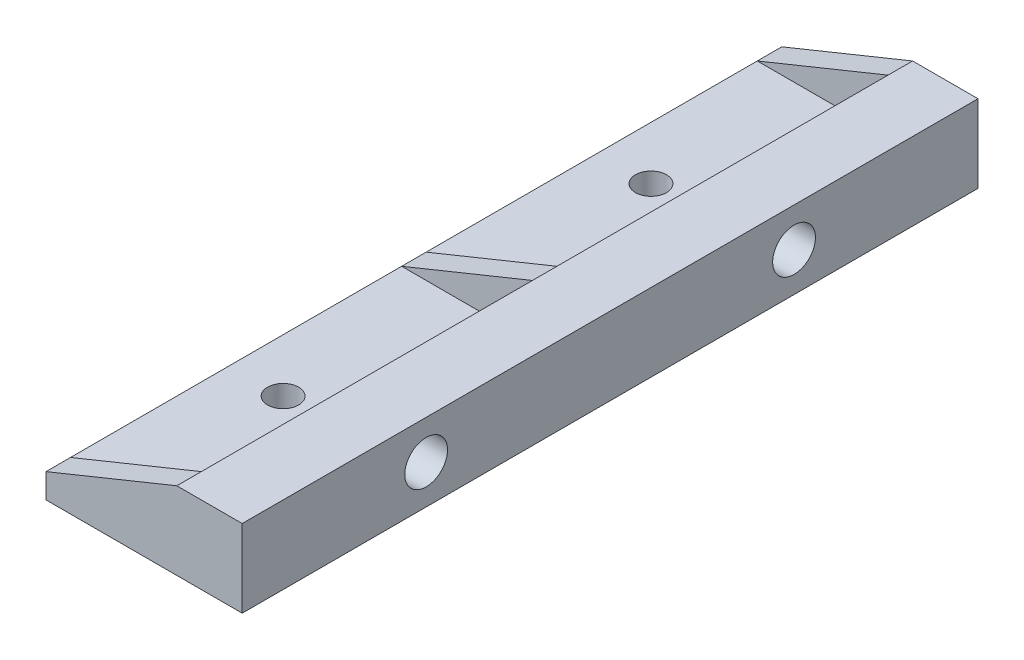
SolidWorks part; units mm, degrees
ref_plane "Front Plane" through (0, 0, 0) normal (0, 0, 1) x (1, 0, 0)
ref_plane "Top Plane" through (0, 0, 0) normal (0, 1, 0) x (1, 0, 0)
ref_plane "Right Plane" through (0, 0, 0) normal (1, 0, 0) x (0, 0, -1)
sketch "Sketch1" plane through (0, 0, 0) normal (0, 0, 1) x (1, 0, 0)
  line L0 (0, 0) -> (0, 9.5)
  line L1 (0, 9.5) -> (-8, 9.5)
  line L2 (-8, 9.5) -> (-8, 6)
  line L3 (-11, 3) -> (-24, 3)
  line L4 (-24, 3) -> (-24, 0)
  line L6 (-24, 0) -> (0, 0)
  arc A0 (-8, 6) -> (-11, 3) centre (-11, 6) cw
  dimension "D1" = 3
  dimension "D2" = 9.5
  dimension "D3" = 24
  dimension "D4" = 8
  dimension "D5" = 3
extrude "Boss-Extrude1" add sketch "Sketch1" along normal blind 90
ref_plane "Plane2" through (0, 0, 0) normal (0, 0, -1) x (-1, 0, 0)
ref_plane "Plane4" through (0, 0, 45) normal (0, 0, -1) x (-1, 0, 0)
sketch "Sketch4" plane through (0, 0, 45) normal (0, 0, -1) x (-1, 0, 0)
  line L0 (8, 9.5) -> (24, 3)
sketch "Sketch5" plane through (0, 0, 0) normal (0, 0, -1) x (-1, 0, 0)
  line L0 (8, 9.5) -> (24, 3)
rib "Rib3" sketch "Sketch4" sketch "Sketch4" thickness 3 extrusion direction parallel to sketch draft on no parameters "D1"=3
rib "Rib4" sketch "Sketch5" sketch "Sketch5" thickness 3 extrusion direction parallel to sketch draft on no parameters "D1"=3
mirror "Mirror1" about plane through (0, 0, 45) normal (0, 0, -1) of "Rib4"
sketch "Sketch6" plane through (0, 0, 0) normal (1, 0, 0) x (0, 0, -1)
  line L0 (-90, 4.75) -> (0, 4.75) construction
  line L1 (-90, 0) -> (-90, 9.5) construction
  line L2 (0, 0) -> (0, 9.5) construction
  circle A0 centre (-67.5, 4.75) radius 2.3495
  circle A1 centre (-22.5, 4.75) radius 2.3495
  point P6 (-67.5, 4.75)
  point P7 (-22.5, 4.75)
  dimension "D3" = 4.699
  dimension "D1" = 22.5
  dimension "D2" = 22.5
sketch "Sketch9" plane through (0, 0, 0) normal (0, -1, 0) x (1, 0, 0)
  line L0 (-17.5, 90) -> (-17.5, 0) construction
  line L1 (-24, 90) -> (0, 90) construction
  line L2 (-24, 0) -> (0, 0) construction
  line L3 (-24, 90) -> (-24, 0) construction
  point P6 (-17.5, 67.5)
  point P7 (-17.5, 22.5)
  dimension "D1" = 22.5
  dimension "D2" = 22.5
  dimension "D3" = 6.5
hole_wizard "#6 Clearance Hole1" positions "Sketch10" profile "Sketch11" hole size "#6" standard "ANSI Inch" end condition through all
sketch "Sketch10" plane through (0, 0, 0) normal (0, -1, 0) x (-1, 0, 0)
  point P0 (17.5, -22.5)
  point P3 (17.5, -67.5)
sketch "Sketch11" plane through (-17.5, 0, 22.5) normal (1, 0, 0) x (0, 0, -1)
  line L0 (0, 0) -> (0, 9.5)
  line L1 (0, 9.5) -> (1.8986, 9.5)
  line L2 (1.8986, 9.5) -> (1.8986, 0)
  line L5 (1.8986, 0) -> (0, 0)
  line L11 (0, -6.35) -> (0, 107.95) construction
  dimension "Thru Hole Dia." = 3.7973
  dimension "Thru Hole Depth" = 9.5
extrude "Cut-Extrude1" cut sketch "Sketch6" against normal offset from surface (7 mm away) 1 up to face at (-8, 7.75, 66.75)
sketch "Sketch12" plane through (0, 0, 0) normal (1, 0, 0) x (0, 0, -1)
  circle A0 centre (-67.5, 4.75) radius 2.6162
  circle A1 centre (-22.5, 4.75) radius 2.6162
  dimension "D1" = 5.2324
extrude "Cut-Extrude2" cut sketch "Sketch12" against normal blind 6.35
